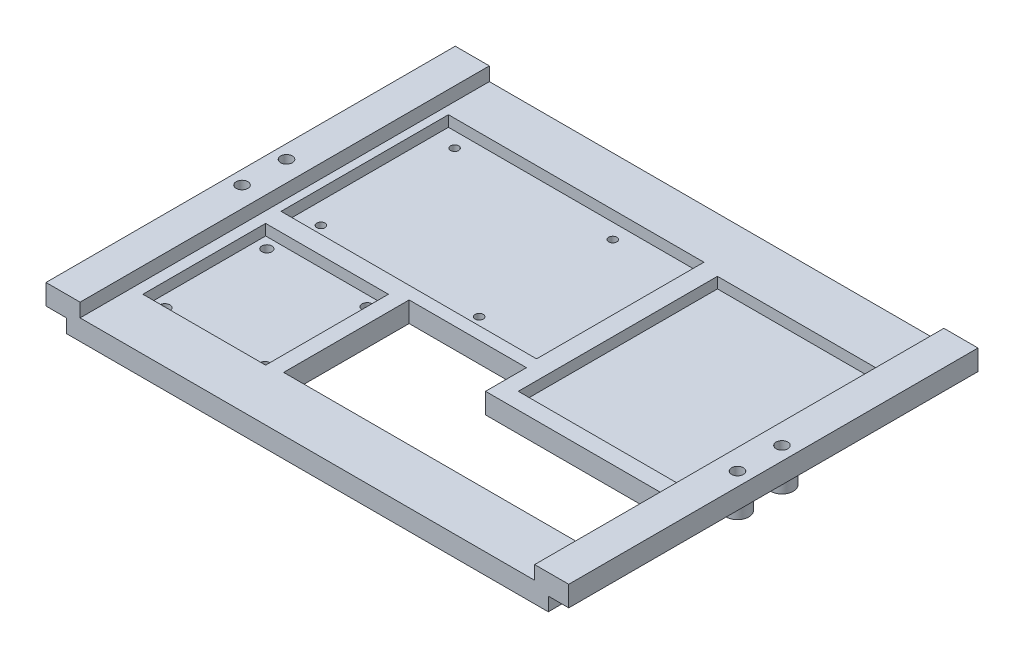
SolidWorks part; units mm, degrees
ref_plane "Front Plane" through (0, 0, 0) normal (0, 0, 1) x (1, 0, 0)
ref_plane "Top Plane" through (0, 0, 0) normal (0, 1, 0) x (1, 0, 0)
ref_plane "Right Plane" through (0, 0, 0) normal (1, 0, 0) x (0, 0, -1)
sketch "Sketch2" plane through (0, 0, 0) normal (0, 0, 1) x (1, 0, 0)
  line L0 (179.1, 12.5) -> (191.6, 12.5)
  line L1 (7.5, 0) -> (184.1, 0)
  line L2 (0, 5) -> (0, 12.5)
  line L3 (0, 12.5) -> (12.5, 12.5)
  line L4 (191.6, 5) -> (191.6, 12.5)
  line L7 (0, 5) -> (7.5, 5)
  line L8 (7.5, 0) -> (7.5, 5)
  line L11 (191.6, 5) -> (184.1, 5)
  line L12 (184.1, 0) -> (184.1, 5)
  line L14 (12.5, 12.5) -> (12.5, 7.5)
  line L15 (12.5, 7.5) -> (179.1, 7.5)
  line L16 (179.1, 12.5) -> (179.1, 7.5)
  dimension "D1" = 191.6
  dimension "D2" = 5
  dimension "D3" = 5
  dimension "D4" = 5
  dimension "D5" = 12.5
  dimension "D6" = 7.5
  dimension "D7" = 7.5
  dimension "D8" = 12.5
  dimension "D9" = 12.5
extrude "PlateFrame" add sketch "Sketch2" along normal blind 150
sketch "Sketch3" plane through (0, 12.5, 0) normal (0, 1, 0) x (1, 0, 0)
  line L0 (12.5, 0) -> (0, 0) construction
  line L2 (0, -150) -> (0, 0) construction
  line L3 (191.6, -150) -> (191.6, 0) construction
  line L4 (191.6, 0) -> (179.1, 0) construction
  circle A0 centre (5, -66.85) radius 2.15
  circle A1 centre (5, -83.15) radius 2.15
  circle A2 centre (186.6, -66.85) radius 2.15
  circle A3 centre (186.6, -83.15) radius 2.15
  dimension "D1" = 4.3
  dimension "D2" = 4.3
  dimension "D3" = 4.3
  dimension "D4" = 4.3
  dimension "D5" = 66.85
  dimension "D6" = 16.3
  dimension "D7" = 5
  dimension "D8" = 5
  dimension "D9" = 5
  dimension "D10" = 181.6
  dimension "D11" = 66.85
  dimension "D12" = 16.3
extrude "HoleSupport" cut sketch "Sketch3" against normal blind 7.5
sketch "Sketch4" plane through (0, 12.5, 0) normal (0, 1, 0) x (1, 0, 0)
  circle A0 centre (5, -66.85) radius 2.15
  circle A1 centre (5, -83.15) radius 2.15
  circle A2 centre (186.6, -83.15) radius 2.15
  circle A3 centre (186.6, -66.85) radius 2.15
  circle A4 centre (186.6, -66.85) radius 4.15
  circle A5 centre (186.6, -83.15) radius 4.15
  circle A6 centre (5, -66.85) radius 4.15
  circle A7 centre (5, -83.15) radius 4.15
  dimension "D1" = 2
extrude "CylindricalSupports" add sketch "Sketch4" against normal blind 12.5
sketch "Sketch5" plane through (0, 7.5, 0) normal (0, 1, 0) x (1, 0, 0)
  line L0 (12.5, -150) -> (12.5, 0) construction
  line L1 (17.5, -87) -> (60.5, -87)
  line L2 (12.5, -150) -> (12.5, 0) construction
  line L3 (17.5, -20) -> (107.15, -20)
  line L4 (17.5, -20) -> (17.5, -77.35)
  line L5 (17.5, -77.35) -> (107.15, -77.35)
  line L6 (107.15, -20) -> (107.15, -77.35)
  line L7 (174.1, -20) -> (116.1, -20)
  line L8 (174.1, -20) -> (174.1, -93)
  line L9 (174.1, -93) -> (116.1, -93)
  line L10 (116.1, -20) -> (116.1, -93)
  line L15 (179.1, -150) -> (179.1, 0) construction
  line L16 (179.1, 0) -> (12.5, 0) construction
  line L17 (17.5, -87) -> (17.5, -130)
  line L18 (17.5, -130) -> (60.5, -130)
  line L19 (60.5, -87) -> (60.5, -130)
  line L20 (179.1, -150) -> (12.5, -150) construction
  dimension "D1" = 5
  dimension "D2" = 89.65
  dimension "D3" = 57.35
  dimension "D4" = 5
  dimension "D5" = 43
  dimension "D6" = 58
  dimension "D7" = 43
  dimension "D8" = 20
  dimension "D9" = 20
  dimension "D10" = 5
  dimension "D11" = 73
  dimension "D12" = 20
extrude "ItemLayout" cut sketch "Sketch5" against normal blind 4
sketch "Sketch6" plane through (0, 7.5, 0) normal (0, 1, 0) x (1, 0, 0)
  line L1 (67.1, -84) -> (110.1, -84)
  line L2 (67.1, -84) -> (67.1, -130)
  line L3 (67.1, -130) -> (110.1, -130)
  line L4 (110.1, -84) -> (110.1, -99)
  line L9 (179.1, -150) -> (179.1, 0) construction
  line L10 (110.1, -130) -> (174.1, -130)
  line L12 (110.1, -99) -> (174.1, -99)
  line L13 (174.1, -130) -> (174.1, -99)
  line L14 (116.1, -93) -> (174.1, -93) construction
  line L15 (116.1, -20) -> (116.1, -93) construction
  line L17 (179.1, -150) -> (12.5, -150) construction
  dimension "D1" = 20
  dimension "D2" = 43
  dimension "D3" = 5
  dimension "D4" = 6
  dimension "D5" = 6
  dimension "D6" = 15
extrude "HoleCutout" cut sketch "Sketch6" against normal blind 7.5
sketch "Sketch7" plane through (0, 3.5, 0) normal (0, 1, 0) x (1, 0, 0)
  line L0 (17.5, -20) -> (17.5, -77.35) construction
  line L1 (17.5, -20) -> (17.5, -77.35) construction
  line L2 (107.15, -20) -> (17.5, -20) construction
  line L3 (107.15, -20) -> (17.5, -20) construction
  circle A0 centre (23.26, -23.5) radius 1.5
  circle A1 centre (23.26, -72.5) radius 1.5
  circle A2 centre (81.26, -72.5) radius 1.5
  circle A3 centre (81.26, -23.5) radius 1.5
  dimension "D1" = 3
  dimension "D2" = 3
  dimension "D3" = 3
  dimension "D4" = 3
  dimension "D5" = 5.76
  dimension "D6" = 5.76
  dimension "D7" = 3.5
  dimension "D8" = 3.5
  dimension "D9" = 58
  dimension "D10" = 58
  dimension "D11" = 49
  dimension "D12" = 49
extrude "HoleRaspberryPi" cut sketch "Sketch7" against normal blind 3.5
sketch "Sketch8" plane through (0, 3.5, 0) normal (0, 1, 0) x (1, 0, 0)
  line L0 (17.5, -130) -> (60.5, -130) construction
  line L1 (60.5, -87) -> (17.5, -87) construction
  line L2 (60.5, -130) -> (60.5, -87) construction
  line L3 (60.5, -130) -> (60.5, -87) construction
  line L4 (17.5, -87) -> (17.5, -130) construction
  line L5 (17.5, -130) -> (60.5, -130) construction
  circle A0 centre (57.56, -127.24) radius 1.85
  circle A1 centre (57.56, -89.86) radius 1.85
  circle A2 centre (20.81, -89.86) radius 1.85
  circle A3 centre (20.81, -127.24) radius 1.85
  dimension "D1" = 3.7
  dimension "D2" = 3.7
  dimension "D3" = 3.7
  dimension "D4" = 3.7
  dimension "D6" = 2.86
  dimension "D8" = 2.94
  dimension "D9" = 2.86
  dimension "D10" = 3.31
  dimension "D11" = 2.76
  dimension "D12" = 3.31
  dimension "D5" = 2.76
  dimension "D7" = 2.94
extrude "HoleMotorDriver" cut sketch "Sketch8" against normal blind 3.5
sketch "Sketch10" plane through (0, 7.5, 0) normal (0, 1, 0) x (1, 0, 0)
  line L1 (17.5, -87) -> (60.5, -87)
  line L2 (17.5, -87) -> (17.5, -130)
  line L3 (17.5, -130) -> (60.5, -130)
  line L4 (60.5, -87) -> (60.5, -130)
  line L5 (16.5, -86) -> (61.5, -86)
  line L6 (16.5, -86) -> (16.5, -131)
  line L7 (16.5, -131) -> (61.5, -131)
  line L8 (61.5, -86) -> (61.5, -131)
  dimension "D1" = 1
  dimension "D2" = 1
  dimension "D3" = 1
  dimension "D4" = 1
extrude "CutMotorDriver" cut sketch "Sketch10" against normal blind 4
sketch "Sketch11" plane through (0, 7.5, 0) normal (0, 1, 0) x (1, 0, 0)
  line L1 (17.5, -20) -> (107.15, -20)
  line L2 (17.5, -20) -> (17.5, -77.35)
  line L3 (17.5, -77.35) -> (107.15, -77.35)
  line L4 (107.15, -20) -> (107.15, -77.35)
  line L5 (109.15, -79.35) -> (15.5, -79.35)
  line L6 (109.15, -79.35) -> (109.15, -18)
  line L7 (109.15, -18) -> (15.5, -18)
  line L8 (15.5, -79.35) -> (15.5, -18)
  dimension "D1" = 2
  dimension "D2" = 2
  dimension "D3" = 2
  dimension "D4" = 2
extrude "CutPaspberryPi" cut sketch "Sketch11" against normal blind 4
